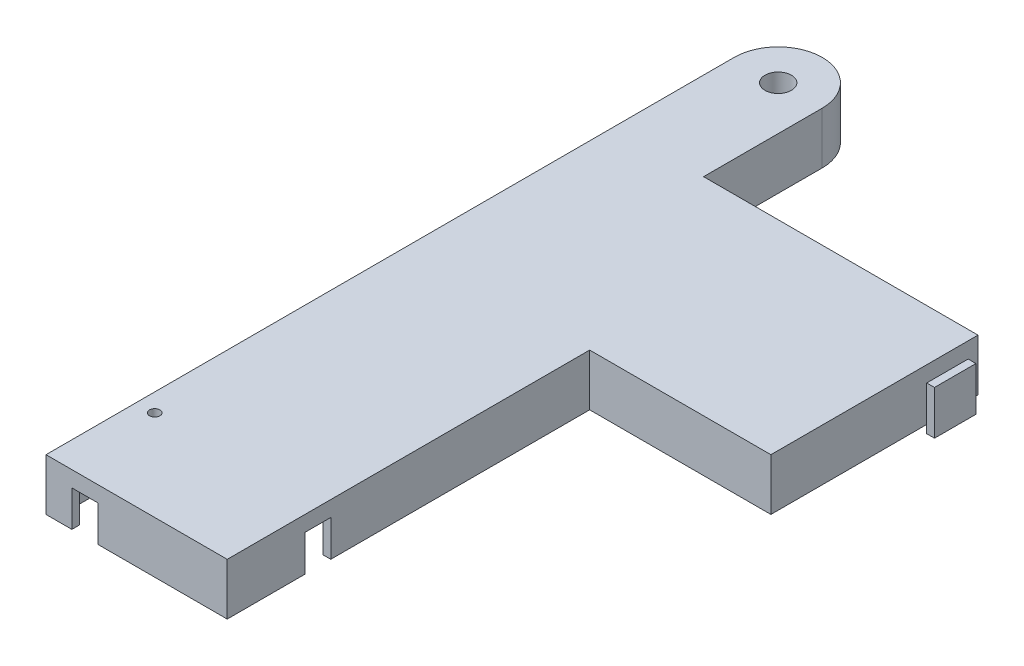
SolidWorks part; units mm, degrees
ref_plane "Front Plane" through (0, 0, 0) normal (0, 0, 1) x (1, 0, 0)
ref_plane "Top Plane" through (0, 0, 0) normal (0, 1, 0) x (1, 0, 0)
ref_plane "Right Plane" through (0, 0, 0) normal (1, 0, 0) x (0, 0, -1)
sketch "CornerrSketch1" plane through (0, 0, 0) normal (0, 1, 0) x (1, 0, 0)
  line L0 (140, 220) -> (140, 140)
  line L2 (0, 0) -> (0, 265.825)
  line L5 (140, 140) -> (70, 140)
  line L6 (70, 140) -> (70, 0)
  line L7 (0, 0) -> (70, 0)
  line L9 (34, 265.825) -> (34, 220)
  line L10 (34, 220) -> (140, 220)
  arc A0 (34, 265.825) -> (0, 265.825) centre (17, 265.825) ccw
  point P2 (17, 282.825)
  point P8 (0, 132.9125)
  dimension "D3" = 34
  dimension "D4" = 80
  dimension "D1" = 220
  dimension "D5" = 45.825
  dimension "D6" = 282.825
  dimension "D7" = 140
  dimension "D11" = 70
extrude "CornerBoss-Extrude1" add sketch "CornerrSketch1" along normal blind 20
shell "Shell2" thickness 3 removed face at (61, 0, -158.5813)
sketch "PadSketch3" plane through (0, 17, 0) normal (0, -1, 0) x (1, 0, 0)
  line L0 (0, -265.825) -> (0, 0) construction
  line L1 (140, -220) -> (34, -220) construction
  circle A0 centre (17, -265.825) radius 12
  circle A1 centre (7, -35) radius 5
  dimension "D1" = 24
  dimension "D2" = 10
  dimension "D3" = 7
  dimension "D4" = 185
extrude "PadBoss-Extrude2" add sketch "PadSketch3" along normal blind 10
sketch "StepperShaftHoleSketch4" plane through (0, 7, 0) normal (0, -1, 0) x (1, 0, 0)
  circle A0 centre (17, -265.825) radius 5.1
  circle A1 centre (7, -35) radius 2
  dimension "D1" = 10.2
  dimension "D2" = 4
extrude "StepperShaftCut-Extrude2" cut sketch "StepperShaftHoleSketch4" against normal through all
sketch "ThreadedNutMountHolesSketch5" plane through (0, 7, 0) normal (0, -1, 0) x (-1, 0, 0)
  circle A8 centre (-17, 273.825) radius 2
  circle A9 centre (-9, 265.825) radius 2
  circle A10 centre (-17, 257.825) radius 2
  circle A11 centre (-25, 265.825) radius 2
  dimension "D1" = 4
  dimension "D2" = 8
  dimension "D3" = 16
  dimension "D5" = 16
extrude "ThreadedNutMountHolesCut-Extrude4" cut sketch "ThreadedNutMountHolesSketch5" against normal blind 10
sketch "TRPegSketch1" plane through (140, 0, 0) normal (1, 0, 0) x (0, 0, -1)
  line L0 (220, 20) -> (220, 0) construction
  line L1 (200.1, 13.9) -> (209.9, 13.9)
  line L2 (200.1, 13.9) -> (200.1, 0)
  line L3 (200.1, 0) -> (209.9, 0)
  line L4 (209.9, 13.9) -> (209.9, 0)
  line L5 (140, 0) -> (220, 0) construction
  point P6 (220, 10)
  dimension "D1" = 10.1
  dimension "D2" = 13.9
  dimension "D3" = 9.8
extrude "TRPegBoss-Extrude1" add sketch "TRPegSketch1" along normal blind 3.1
sketch "TRPegCapSketch2" plane through (143.1, 0, 0) normal (1, 0, 0) x (0, 0, -1)
  line L0 (200.1, 0) -> (209.9, 0) construction
  line L1 (197.1, 17) -> (213.1, 17)
  line L2 (197.1, 17) -> (197.1, 0)
  line L3 (197.1, 0) -> (213.1, 0)
  line L4 (213.1, 17) -> (213.1, 0)
  line L5 (200.1, 13.9) -> (200.1, 0) construction
  dimension "D1" = 16
  dimension "D2" = 3
  dimension "D3" = 17
extrude "TRPegCapBoss-Extrude2" add sketch "TRPegCapSketch2" along normal blind 3
sketch "BottomPegHoleSketch3" plane through (0, 0, 0) normal (0, 0, 1) x (1, 0, 0)
  line L0 (0, 0) -> (70, 0) construction
  line L1 (10, 13.9) -> (20, 13.9)
  line L2 (10, 13.9) -> (10, 0)
  line L3 (10, 0) -> (20, 0)
  line L4 (20, 13.9) -> (20, 0)
  line L5 (0, 20) -> (0, 0) construction
  line L6 (143.1, 13.9) -> (140, 13.9) construction
  dimension "D2" = 10
  dimension "D3" = 10
extrude "BottomPegHoleCut-Extrude1" cut sketch "BottomPegHoleSketch3" against normal blind 3
sketch "BedCenterPegHoleCutSketch1" plane through (70, 0, 0) normal (1, 0, 0) x (0, 0, -1)
  line L0 (0, 0) -> (140, 0) construction
  line L1 (30, 14) -> (40, 14)
  line L2 (30, 14) -> (30, 0)
  line L3 (30, 0) -> (40, 0)
  line L4 (40, 14) -> (40, 0)
  line L5 (140, 20) -> (140, 0) construction
  dimension "D2" = 10
  dimension "D1" = 14
  dimension "D3" = 100
extrude "BedCenterPegHoleCut-Extrude1" cut sketch "BedCenterPegHoleCutSketch1" against normal blind 3
equation "\"RailThickness\"= .125in'Spec"
equation "\"StepperMountingHoleDistance\"= 31mm'Spec"
equation "\"StepperMountingHoleOffsetFromLeftOrRightSide\"= \"StepperMountingHoleOffsetFromItsSide\" + \"RailThickness\""
equation "\"StepperMountingHoleOffsetFromItsSide\"= 5.5mm'Spec"
equation "\"FrontBackRailLength\"= 510mm"
equation "\"DistanceBetweenLeftToRightStepperHoles\"= \"FrontBackRailLength\" - \"StepperMountingHoleOffsetFromLeftOrRightSide\" * 2 - \"StepperMountingHoleDistance\"'Equals 461.65"
equation "\"BedThickness\"= 20mm"
equation "\"BedLLongSide\"= \"BedThirdSize\" * 3'Equals 210"
equation "\"BedLShortSide\"= \"BedThirdSize\" * 2'Equals 140"
equation "\"BedLWidth\"= \"BedThirdSize\"'Equals 70"
equation "\"D4@CornerrSketch1\"=\"BedLWidth\" + \"BedIncreasedByWidth\"/2"
equation "\"D1@CornerrSketch1\" = \"BedLLongSide\" + \"BedIncreasedByWidth\" / 2"
equation "\"BedInnerSquareWidth\"= \"BedThirdSize\" * 3'Equals 210"
equation "\"BedWidth\"= \"BedInnerSquareWidth\" + \"BedLWidth\" * 2 + \"BedIncreasedByWidth\"'Equals 370"
equation "\"BedIncreasedByWidth\"= 20mm"
equation "\"BedIncreasedByLength\"= 0mm"
equation "\"BedThirdSize\"= 70mm"
equation "\"D1@TRPegCapSketch2\"=\"BedPegCapWidth\""
equation "\"StandardWallThickness\"= 3mm"
equation "\"D2@TRPegCapSketch2\" = \"StandardWallThickness\""
equation "\"D3@TRPegCapSketch2\"=\"BedPegCapHeight\""
equation "\"D1@TRPegCapBoss-Extrude2\" = \"StandardWallThickness\""
equation "\"D1@BottomPegHoleCut-Extrude1\"=\"StandardWallThickness\""
equation "\"D1@Shell2\"=\"StandardWallThickness\""
equation "\"D2@TRPegSketch1\"=\"BedPegHeight\""
equation "\"D5@CornerrSketch1\"=\"DistanceFromBedSideToStepperHole\""
equation "\"DistanceFromBedFrontToStepperHole\"= \"LeadScrewNutPadSize\" + 10mm"
equation "\"DistanceFromBedSideToStepperHole\"= ( \"DistanceBetweenLeftToRightStepperHoles\" - \"BedWidth\" ) / 2'Equals 45.825"
equation "\"D7@CornerrSketch1\"= \"BedLShortSide\" + \"BedIncreasedByLength\" / 2"
equation "\"D3@CornerrSketch1\"=\"DistanceFromBedFrontToStepperHole\""
equation "\"BedToBuildPlateStandoffPadSize\"= 10mm"
equation "\"LeadScrewNutPadSize\"= \"LeadScrewNutMountingHoleFlangeDiameter\" + 2mm'Equals 24"
equation "\"D1@PadSketch3\" = \"LeadScrewNutPadSize\""
equation "\"D1@StepperShaftHoleSketch4\"=\"LeadScrewNutInnerShaftFlangeDiameter\""
equation "\"D11@CornerrSketch1\"=\"BedLWidth\""
equation "\"LeadScrewNutInnerShaftFlangeDiameter\"= 10.2mm'Spec"
equation "\"LeadScrewNutMountHoleDiameter\"= \"M3HeatInsertHoleDiameter\""
equation "\"LeadScrewNutMountingHoleFlangeDiameter\"= 22mm'Spec"
equation "\"LeadScrewNutMountingHoleDistance\"= 16mm'Spec"
equation "\"D2@ThreadedNutMountHolesSketch5\"=\"LeadScrewNutMountingHoleDistance\" / 2"
equation "\"D3@ThreadedNutMountHolesSketch5\"=\"LeadScrewNutMountingHoleDistance\""
equation "\"D5@ThreadedNutMountHolesSketch5\"=\"LeadScrewNutMountingHoleDistance\""
equation "\"D4@ThreadedNutMountHolesSketch5\"=\"LeadScrewNutMountingHoleDistance\"/2"
equation "\"D1@ThreadedNutMountHolesSketch5\"=\"LeadScrewNutMountHoleDiameter\""
equation "\"LeadScrewNutPadDepth\"= \"BedThickness\" / 2'Equals 10"
equation "\"D1@ThreadedNutMountHolesCut-Extrude4\"=\"LeadScrewNutPadDepth\""
equation "\"D2@PadSketch3\"=\"BedToBuildPlateStandoffPadSize\""
equation "\"D3@PadSketch3\"=\"BedToBuildPlateStandoffHolesDistanceFromFront\""
equation "\"BuildPlateWidth\"= 350mm'Spec"
equation "\"D4@PadSketch3\"=\"BedIncreasedByWidth\"/2 + \"BuildPlateWidth\"/2"
equation "\"D2@StepperShaftHoleSketch4\"=\"M3HeatInsertHoleDiameter\""
equation "\"BuildPlateStandoffHolesDistanceFromFront\"= 7mm"
equation "\"BedToBuildPlateStandoffHolesDistanceFromFront\"= \"BuildPlateStandoffHolesDistanceFromFront\" + \"BedIncreasedByLength\" / 2'Equals 7"
equation "\"BedPegHoleWidth\"= 10mm"
equation "\"BedPegHoleHeight\"= \"BedThickness\" - \"StandardWallThickness\" * 2'Equals 14"
equation "\"BedPegWidth\"= \"BedPegHoleWidth\" - .1mm * 2'For easier assembly"
equation "\"BedPegHeight\"= \"BedPegHoleHeight\" - .1mm'For easier assembly"
equation "\"BedTopPegOffsetFromSide\"= 10mm"
equation "\"BedPegBoss\"= \"StandardWallThickness\" + .1mm'For easier assembly"
equation "\"BedPegCapHeight\"= \"BedThickness\" - \"StandardWallThickness\"'Equals 17"
equation "\"BedPegCapWidth\"= \"BedThickness\" / 2 + \"StandardWallThickness\" * 2'Equals 16"
equation "\"D1@TRPegSketch1\"=\"BedTopPegOffsetFromSide\" + .1mm"
equation "\"D3@TRPegSketch1\"= \"BedPegWidth\""
equation "\"D1@TRPegBoss-Extrude1\"=\"BedPegBoss\""
equation "\"D3@BottomPegHoleSketch3\"=\"BedTopPegOffsetFromSide\""
equation "\"D2@BottomPegHoleSketch3\"=\"BedPegHoleWidth\""
equation "\"D1@BedCenterPegHoleCutSketch1\" = \"BedPegHoleHeight\""
equation "\"D2@BedCenterPegHoleCutSketch1\" = \"BedPegHoleWidth\""
equation "\"D3@BedCenterPegHoleCutSketch1\" = \"BedInnerSquareWidth\" / 2 - \"BedPegHoleWidth\" / 2"
equation "\"D1@BedCenterPegHoleCut-Extrude1\"=\"StandardWallThickness\""
equation "\"M3HeatInsertHoleDiameter\"= 4mm'Spec"
